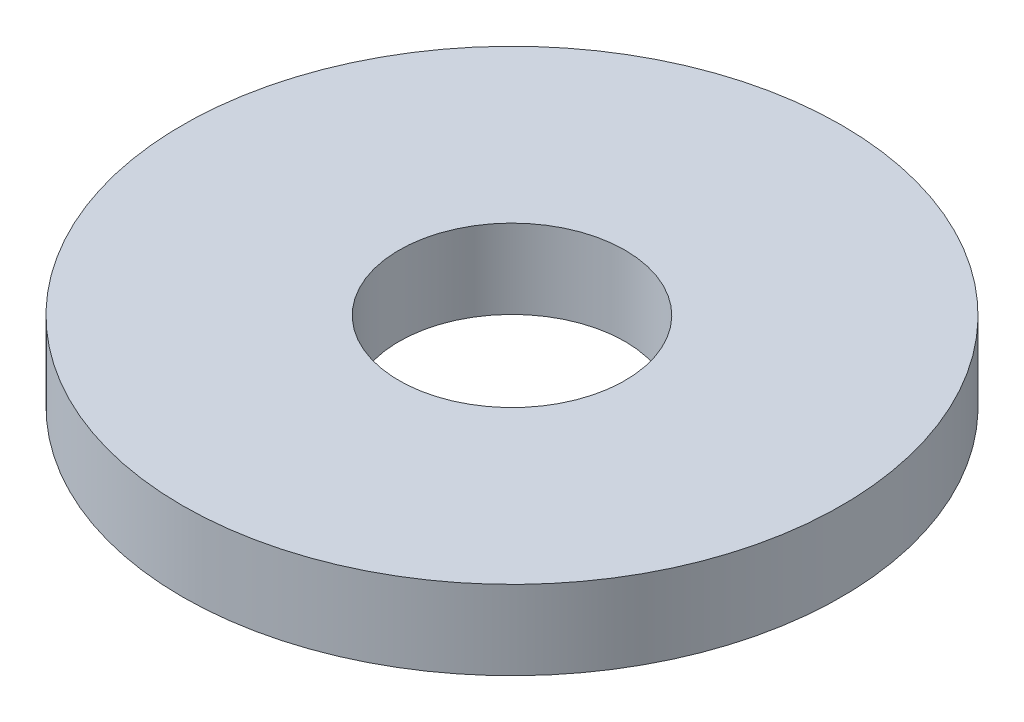
SolidWorks part; units mm, degrees
ref_plane "Front Plane" through (0, 0, 0) normal (0, 0, 1) x (1, 0, 0)
ref_plane "Top Plane" through (0, 0, 0) normal (0, 1, 0) x (1, 0, 0)
ref_plane "Right Plane" through (0, 0, 0) normal (1, 0, 0) x (0, 0, -1)
sketch "Sketch1" plane through (0, 0, 0) normal (0, 1, 0) x (1, 0, 0)
  circle A0 centre (0, 0) radius 87.5
  dimension "FLANGE_OD" = 175
extrude "Boss-Extrude1" add sketch "Sketch1" along normal blind 21
sketch "Sketch2" plane through (0, 0, 0) normal (0, 1, 0) x (1, 0, 0)
  circle A0 centre (0, 0) radius 30
  dimension "BORE_D" = 60
extrude "Cut-Extrude1" cut sketch "Sketch2" along normal through all
sketch "Sketch3" plane through (0, 21, 0) normal (0, 1, 0) x (1, 0, 0)
  circle A0 centre (0, 0) radius 22.8717 construction
  circle A1 centre (-22.8717, 0) radius 3.413
  dimension "BOLT_D" = 6.826
  dimension "BOLT_PCD" = 45.7434
extrude "Cut-Extrude2" cut sketch "Sketch3" against normal blind 15.8477 rebuild error yes
pattern_circular "CirPattern1" count 5 over 360 rebuild error yes
